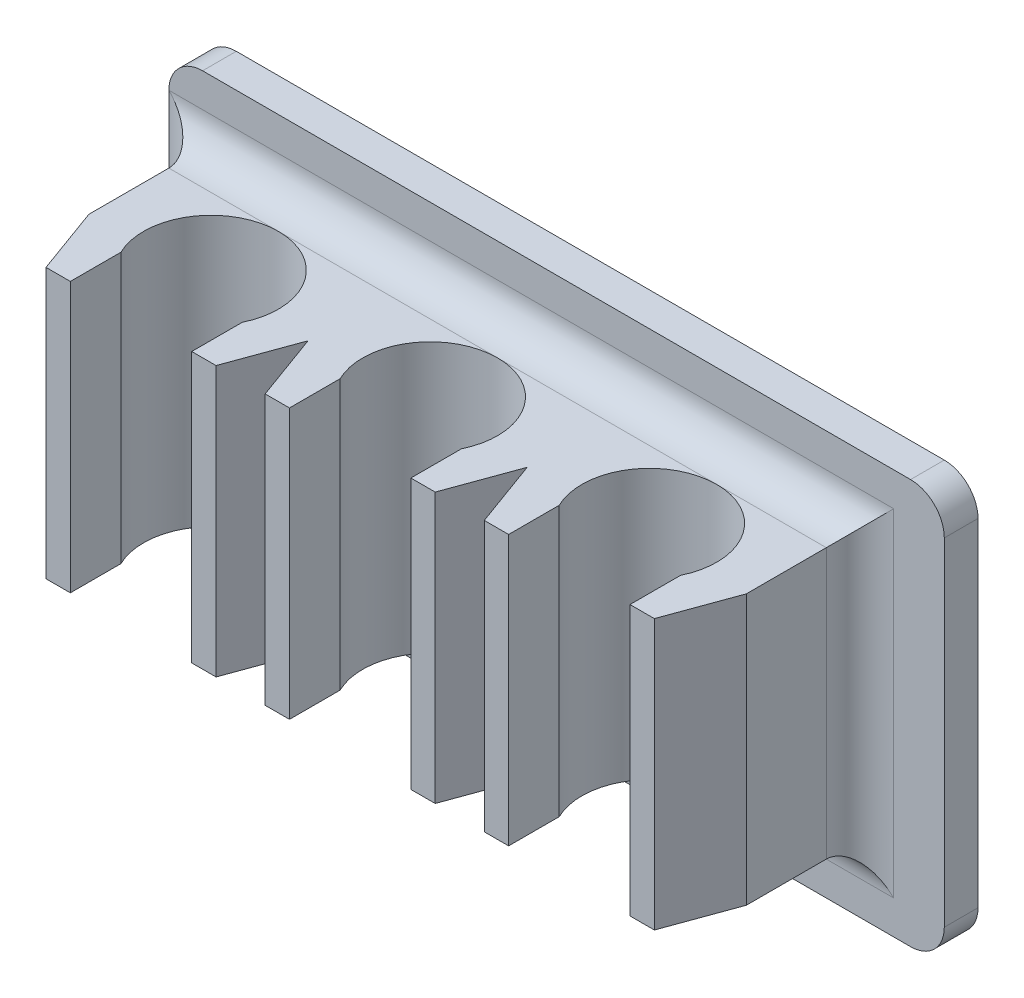
SolidWorks part; units mm, degrees
ref_plane "Front Plane" through (0, 0, 0) normal (0, 0, 1) x (1, 0, 0)
ref_plane "Top Plane" through (0, 0, 0) normal (0, 1, 0) x (1, 0, 0)
ref_plane "Right Plane" through (0, 0, 0) normal (1, 0, 0) x (0, 0, -1)
sketch "Sketch1" plane through (0, 0, 0) normal (0, 0, 1) x (1, 0, 0)
  line L1 (11.5, -6) -> (-11.5, -6)
  line L2 (11.5, -6) -> (11.5, 6)
  line L3 (11.5, 6) -> (-11.5, 6)
  line L4 (-11.5, -6) -> (-11.5, 6)
  line L5 (11.5, -6) -> (-11.5, 6) construction
  line L6 (11.5, 6) -> (-11.5, -6) construction
  point P0 (0, 0)
  dimension "D1" = 12
  dimension "D2" = 23
extrude "Boss-Extrude1" add sketch "Sketch1" along normal blind 1
sketch "Sketch3" plane through (0, 0, 0) normal (0, -1, 0) x (1, 0, 0)
  line L0 (-10.5, 1) -> (-10.5, 4.3718)
  line L1 (-11.5, 1) -> (11.5, 1) construction
  line L2 (-9.7721, 6.3718) -> (-9.05, 6.3718)
  line L3 (-9.05, 6.3718) -> (-9.05, 4.8718)
  line L4 (-7.25, 4) -> (-7.25, 1) construction
  line L5 (-5.45, 6.3718) -> (-5.45, 4.8718)
  line L8 (-11.5, 1) -> (-11.5, 0) construction
  line L9 (-10.5, 1) -> (-4, 1)
  line L10 (-10.5, 4.3718) -> (-9.7721, 6.3718)
  line L11 (-4, 1) -> (-4, 4.3718)
  line L12 (-4, 4.3718) -> (-4.7279, 6.3718)
  line L13 (-4.7279, 6.3718) -> (-5.45, 6.3718)
  arc A0 (-9.05, 4.8718) -> (-5.45, 4.8718) centre (-7.25, 4) ccw
  arc A1 (-5.45, 4.8718) -> (-9.05, 4.8718) centre (-7.25, 4) ccw construction
  point P4 (-10.5, 6.3718)
  dimension "D1" = 4
  dimension "D2" = 3.6
  dimension "D3" = 1.5
  dimension "D4" = 6.5
  dimension "D5" = 3
  dimension "D6" = 1
  dimension "D7" = 2
  dimension "D8" = 20
extrude "Boss-Extrude2" add sketch "Sketch3" along normal mid plane 8
pattern_linear "LPattern2" count 3 spacing 6.5 along (1, 0, 0) of "Boss-Extrude2"
fillet "Fillet1" radius 1 4 edges at (11.5, 6, 0.5) (11.5, -6, 0.5) (-11.5, 6, 0.5) (-11.5, -6, 0.5)
fillet "Fillet2" radius 1 4 edges at (-10.5, 0, 1) (-0.75, -4, 1) (9, 0, 1) (-0.75, 4, 1)
